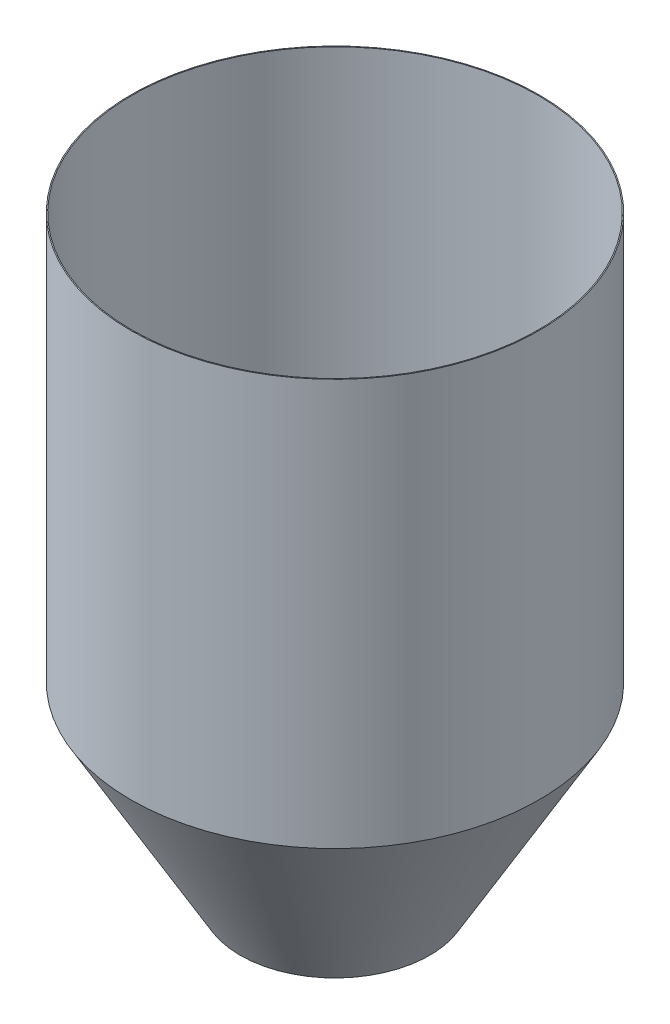
SolidWorks part; units mm, degrees
material "5052-H36"
ref_plane "Front Plane" through (0, 0, 0) normal (0, 0, 1) x (1, 0, 0)
ref_plane "Top Plane" through (0, 0, 0) normal (0, 1, 0) x (1, 0, 0)
ref_plane "Right Plane" through (0, 0, 0) normal (1, 0, 0) x (0, 0, -1)
sketch "Sketch1" plane through (0, 0, 0) normal (0, 1, 0) x (1, 0, 0)
  circle A0 centre (0, 0) radius 254
  circle A1 centre (0, 0) radius 255.2141
  dimension "D1" = 508
  dimension "D2" = 1.2141
extrude "Boss-Extrude1" add sketch "Sketch1" along normal blind 508
sketch "Sketch2" plane through (0, 0, 0) normal (0, 0, 1) x (1, 0, 0)
  line L0 (254, 0) -> (117.3176, -236.7409)
  line L1 (254, 0) -> (0, -439.9409) construction
  line L2 (0, -439.9409) -> (0, 0) construction
  line L3 (254, 0) -> (-254, 0) construction
  line L4 (117.3176, -236.7409) -> (118.5317, -236.7409)
  line L5 (118.5317, -236.7409) -> (255.2141, 0)
  line L6 (255.2141, 0) -> (254, 0)
  line L7 (254, 0) -> (254, 508) construction
  dimension "D1" = 203.2
  dimension "D2" = 508
  dimension "D3" = 508
revolve "Revolve1" add sketch "Sketch2" angle 360 about L2
equation "\"D3@Sketch2\"=\"D2@Sketch2\""
